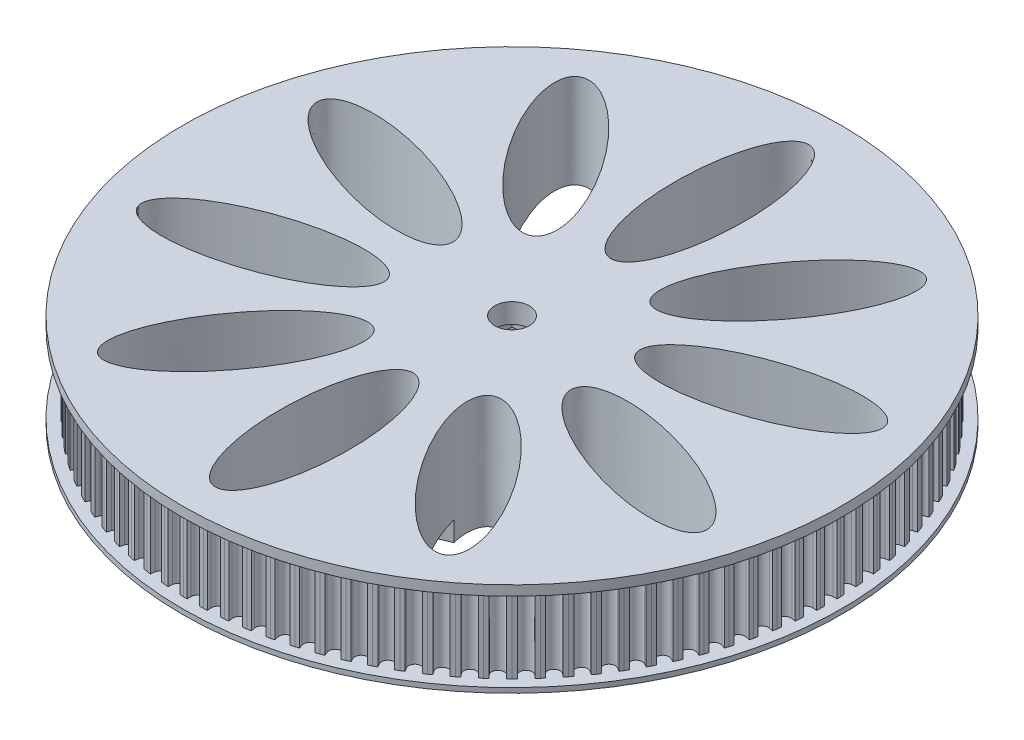
SolidWorks part; units mm, degrees
ref_plane "Front Plane" through (0, 0, 0) normal (0, 0, 1) x (1, 0, 0)
ref_plane "Top Plane" through (0, 0, 0) normal (0, 1, 0) x (1, 0, 0)
ref_plane "Right Plane" through (0, 0, 0) normal (1, 0, 0) x (0, 0, -1)
sketch "Sketch1" plane through (0, 0, 0) normal (0, 1, 0) x (1, 0, 0)
  circle A0 centre (0, 0) radius 33.331
  circle A1 centre (0, 0) radius 8.55
  ellipse E0 centre (0, 20) end of major axis (0, 30) minor radius 3.5
  ellipse E1 centre (11.7557, 16.1803) end of major axis (17.6336, 24.2705) minor radius 3.5
  ellipse E2 centre (19.0211, 6.1803) end of major axis (9.5106, 3.0902) minor radius 3.5
  ellipse E3 centre (19.0211, -6.1803) end of major axis (28.5317, -9.2705) minor radius 3.5
  ellipse E4 centre (11.7557, -16.1803) end of major axis (17.6336, -24.2705) minor radius 3.5
  ellipse E5 centre (0, -20) end of major axis (0, -10) minor radius 3.5
  ellipse E6 centre (-11.7557, -16.1803) end of major axis (-17.6336, -24.2705) minor radius 3.5
  ellipse E7 centre (-19.0211, -6.1803) end of major axis (-28.5317, -9.2705) minor radius 3.5
  ellipse E8 centre (-19.0211, 6.1803) end of major axis (-28.5317, 9.2705) minor radius 3.5
  ellipse E9 centre (-11.7557, 16.1803) end of major axis (-17.6336, 24.2705) minor radius 3.5
  point P66 (0, 0)
  dimension "D1" = 66.662
  dimension "D2" = 17.1
  dimension "D3" = 20
  dimension "D4" = 7
  dimension "D5" = 20
  dimension "D6" = 10
extrude "Boss-Extrude1" add sketch "Sketch1" along normal blind 11.5
sketch "Sketch2" plane through (0, 11.5, 0) normal (0, 1, 0) x (1, 0, 0)
  circle A0 centre (0, 0) radius 8.55
  circle A1 centre (0, 0) radius 8.55 construction
  circle A2 centre (0, 0) radius 1.75
  dimension "D1" = 3.5
extrude "Boss-Extrude2" add sketch "Sketch2" against normal blind 2
sketch "Sketch3" plane through (0, 9.5, 0) normal (0, -1, 0) x (-1, 0, 0)
  line L1 (6.0458, 6.0458) -> (-6.0458, 6.0458)
  line L2 (6.0458, 6.0458) -> (6.0458, -6.0458)
  line L3 (6.0458, -6.0458) -> (-6.0458, -6.0458)
  line L4 (-6.0458, 6.0458) -> (-6.0458, -6.0458)
  line L5 (6.0458, 6.0458) -> (-6.0458, -6.0458) construction
  line L6 (6.0458, -6.0458) -> (-6.0458, 6.0458) construction
  circle A0 centre (0, 0) radius 8.55 construction
  circle A1 centre (0, 0) radius 8.55 construction
  circle A2 centre (0, 0) radius 8.55
  point P0 (0, 0)
  circle M6 centre (0, 0) radius 8.55
extrude "Boss-Extrude3" add sketch "Sketch3" along normal blind 5 contours L3 M6 | L2 M6 | L4 M6 | L1 M6 region at (-7.0612, 9.5, 0) region at (0, 9.5, -7.0612) region at (7.0612, 9.5, 0) region at (0, 9.5, 7.0612)
sketch "Sketch4" plane through (0, 0, 0) normal (0, -1, 0) x (-1, 0, 0)
  circle A0 centre (0, 0) radius 12.55
  circle A1 centre (0, 0) radius 33.331
  circle A2 centre (0, 0) radius 33.331 construction
  arc A3 (-6.0458, 6.0458) -> (-6.0458, -6.0458) centre (0, 0) ccw construction
  dimension "D1" = 4
extrude "Cut-Extrude1" cut sketch "Sketch4" against normal blind 2 contours A1 | A0
sketch "Sketch5" plane through (0, 11.5, 0) normal (0, 1, 0) x (1, 0, 0)
  line L0 (0.63, 32.231) -> (2, 32.231)
  line L1 (-2, 32.231) -> (-0.63, 32.231)
  line L2 (-2, 32.231) -> (-2, 35.231)
  line L3 (-2, 35.231) -> (2, 35.231)
  line L4 (2, 32.231) -> (2, 35.231)
  line L5 (-0.63, 31.831) -> (-0.63, 32.231)
  line L6 (0.63, 31.831) -> (0.63, 32.231)
  arc A1 (-0.63, 31.831) -> (0.63, 31.831) centre (0, 31.831) ccw
  point P12 (0, 35.231)
  circle M9 centre (0, 0) radius 33.331
  dimension "D2" = 1.26
  dimension "D3" = 4
  dimension "D1" = 31.831
  dimension "D4" = 0.4
  dimension "D5" = 3
extrude "Cut-Extrude2" cut sketch "Sketch5" against normal blind 8 from offset 1 contours L5 A1 L6 L0 L4 L2 L1 M9 | L4 L3 L2 M9 region at (0, 11.5, -32.5645) region at (0, 11.5, -34.2709) offset against normal yes
pattern_circular "CirPattern1" count 100 over 360 about axis through (0, 9.5, 0) along (0, 1, 0) of "Cut-Extrude2" reverse direction yes
equation "\"pitch\"= 2"
equation "\"amount_of_teeth\" = 100"
equation "\"pitch_diameter\"= ( \"pitch\" * \"amount_of_teeth\" ) / pi"
equation "\"D1@Sketch1\"=\"pitch_diameter\"+3"
equation "\"D1@CirPattern1\"=\"amount_of_teeth\""
equation "\"D1@Sketch5\"=\"pitch_diameter\"/2"
